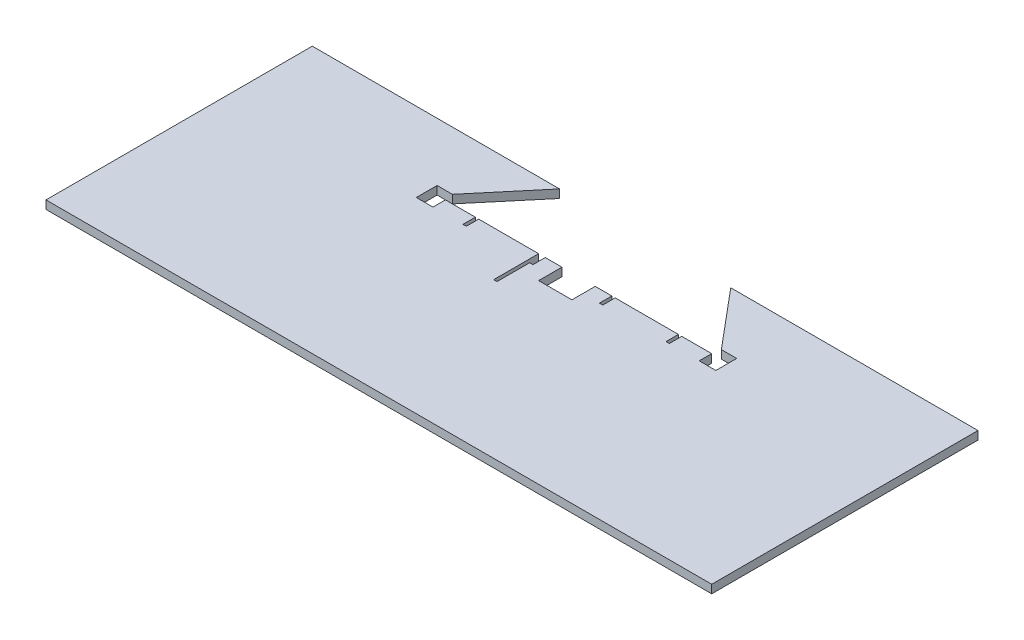
SolidWorks part; units mm, degrees
material "Depron"
ref_plane "Front Plane" through (0, 0, 0) normal (0, 0, 1) x (1, 0, 0)
ref_plane "Top Plane" through (0, 0, 0) normal (0, 1, 0) x (1, 0, 0)
ref_plane "Right Plane" through (0, 0, 0) normal (1, 0, 0) x (0, 0, -1)
sketch "Sketch1" plane through (0, 0, 0) normal (0, 1, 0) x (1, 0, 0)
  line L0 (32.6619, 101.6) -> (127, 101.6)
  line L1 (-127, 0) -> (127, 0)
  line L2 (-127, 0) -> (-127, 101.6)
  line L3 (-127, 101.6) -> (-32.6619, 101.6)
  line L4 (127, 0) -> (127, 101.6)
  line L5 (0, -898.4) -> (0, 49101.6) construction
  line L6 (-53.975, 76.2) -> (-32.6619, 101.6)
  line L7 (-53.975, 76.2) -> (53.975, 76.2)
  line L8 (53.975, 76.2) -> (32.6619, 101.6)
  line L9 (-1003.9539, 76.2) -> (48996.0461, 76.2) construction
  point P11 (0, 76.2)
  dimension "D1" = 101.6
  dimension "D2" = 254
  dimension "D4" = 107.95
  dimension "D6" = 25.4
  dimension "angle1" = 50
extrude "Boss-Extrude1" add sketch "Sketch1" along normal blind 3.175
sketch "Sketch2" plane through (0, 3.175, 0) normal (0, 1, 0) x (-1, 0, 0)
  line L0 (0, 0) -> (0, -134.62) construction
  line L1 (127, 0) -> (-127, 0) construction
  line L2 (-53.975, -76.2) -> (53.975, -76.2) construction
  line L3 (39.37, -76.2) -> (38.1, -76.2)
  line L4 (39.37, -76.2) -> (39.37, -71.4756)
  line L5 (39.37, -71.4756) -> (38.1, -71.4756)
  line L6 (38.1, -76.2) -> (38.1, -71.4756)
  line L7 (13.97, -76.2) -> (12.7, -76.2)
  line L8 (-53.975, -76.2) -> (53.975, -76.2) construction
  line L9 (13.97, -71.4756) -> (12.7, -71.4756)
  line L10 (12.7, -76.2) -> (12.7, -71.4756)
  line L11 (-12.7, -76.2) -> (-12.7, -71.4756)
  line L12 (-13.97, -71.4756) -> (-12.7, -71.4756)
  line L13 (-13.97, -76.2) -> (-13.97, -71.4756)
  line L14 (-13.97, -76.2) -> (-12.7, -76.2)
  line L15 (-38.1, -76.2) -> (-38.1, -71.4756)
  line L16 (-39.37, -71.4756) -> (-38.1, -71.4756)
  line L17 (-39.37, -76.2) -> (-39.37, -71.4756)
  line L18 (-39.37, -76.2) -> (-38.1, -76.2)
  line L19 (6.35, -76.2) -> (-6.35, -76.2)
  line L20 (13.97, -76.2) -> (15.24, -76.2)
  line L21 (13.97, -71.4756) -> (13.97, -59.055)
  line L22 (13.97, -59.055) -> (15.24, -59.055)
  line L23 (15.24, -76.2) -> (15.24, -59.055)
  line L24 (6.35, -76.2) -> (6.35, -67.31)
  line L25 (6.35, -67.31) -> (-6.35, -67.31)
  line L26 (-6.35, -76.2) -> (-6.35, -67.31)
  line L27 (-53.975, -76.2) -> (-51.3109, -79.375)
  line L28 (50.8, -80.9625) -> (57.15, -80.9625) construction
  line L29 (50.8, -80.9625) -> (50.8, -71.4375) construction
  line L30 (50.8, -71.4375) -> (57.15, -71.4375)
  line L31 (57.15, -80.9625) -> (57.15, -71.4375) construction
  line L32 (50.8, -80.9625) -> (57.15, -71.4375) construction
  line L33 (50.8, -71.4375) -> (57.15, -80.9625) construction
  line L34 (-50.8, -76.2) -> (-53.975, -76.2)
  line L35 (-50.8, -76.2) -> (-50.8, -71.4375)
  line L36 (-50.8, -71.4375) -> (-57.15, -71.4375)
  line L37 (53.975, -76.2) -> (32.6619, -101.6) construction
  line L38 (53.975, -76.2) -> (51.3109, -79.375)
  line L39 (51.3109, -79.375) -> (57.15, -79.375)
  line L40 (57.15, -79.375) -> (57.15, -71.4375)
  line L41 (50.8, -76.2) -> (50.8, -71.4375)
  line L42 (50.8, -76.2) -> (53.975, -76.2)
  line L43 (-57.15, -79.375) -> (-57.15, -71.4375)
  line L44 (-51.3109, -79.375) -> (-57.15, -79.375)
  point P31 (0, -67.31)
  point P32 (53.975, -76.2)
  line M6 (-53.975, -76.2) -> (53.975, -76.2)
  line M38 (-32.6619, -101.6) -> (-53.975, -76.2)
  line M39 (53.975, -76.2) -> (32.6619, -101.6)
  dimension "D1" = 1.27
  dimension "D2" = 4.7244
  dimension "D3" = 1.27
  dimension "D4" = 4.7244
  dimension "D5" = 1.27
  dimension "D6" = 17.145
  dimension "D7" = 12.7
  dimension "D8" = 38.1
  dimension "D9" = 12.7
  dimension "D10" = 8.89
  dimension "D11" = 6.35
  dimension "D12" = 9.525
  dimension "D13" = 3.175
ref_plane "Center Plane" through (0, 0, 0) normal (1, 0, 0) x (0, 0, -1)
sketch "Sketch3" plane through (0, 3.175, 0) normal (0, 1, 0) x (1, 0, 0)
  line L0 (-38.735, 71.4756) -> (-38.735, 76.2)
  line L1 (-39.37, 71.4756) -> (-38.1, 71.4756) construction
  line L2 (-39.37, 76.2) -> (-38.1, 76.2) construction
  line L3 (-14.605, 76.2) -> (-14.605, 59.055)
  line L4 (-13.97, 76.2) -> (-15.24, 76.2) construction
  line L5 (-13.97, 59.055) -> (-15.24, 59.055) construction
  line L6 (-13.335, 71.4756) -> (-13.335, 76.2)
  line L7 (-13.97, 71.4756) -> (-12.7, 71.4756) construction
  line L8 (-13.97, 76.2) -> (-12.7, 76.2) construction
  line L9 (-6.35, 76.2) -> (-6.35, 67.31)
  line L10 (-6.35, 67.31) -> (6.35, 67.31)
  line L11 (6.35, 67.31) -> (6.35, 76.2)
  line L12 (13.335, 71.4756) -> (13.335, 76.2)
  line L13 (13.97, 71.4756) -> (12.7, 71.4756) construction
  line L14 (13.97, 76.2) -> (12.7, 76.2) construction
  line L15 (38.735, 71.4756) -> (38.735, 76.2)
  line L16 (39.37, 71.4756) -> (38.1, 71.4756) construction
  line L17 (39.37, 76.2) -> (38.1, 76.2) construction
extrude "Cut-Extrude1" cut sketch "Sketch2" against normal up to surface (3.175 mm away) contours L6 L4 L5 M6 | L23 L22 L21 L9 L10 M6 | L26 L24 L25 M6 | L13 L11 L12 M6 | L17 L15 L16 M6 | L41 L39 L40 L30 M6 M39 | L44 L35 L36 L43 M38 M6 region at (54.2499, 3.175, -75.1437) region at (38.735, 3.175, -73.8378) region at (13.335, 3.175, -73.8378) region at (0, 3.175, -71.755) region at (-14.3306, 3.175, -68.9691) region at (-38.735, 3.175, -73.8378) region at (-54.2499, 3.175, -75.1437) up to face at (0, 0, -69.85)
